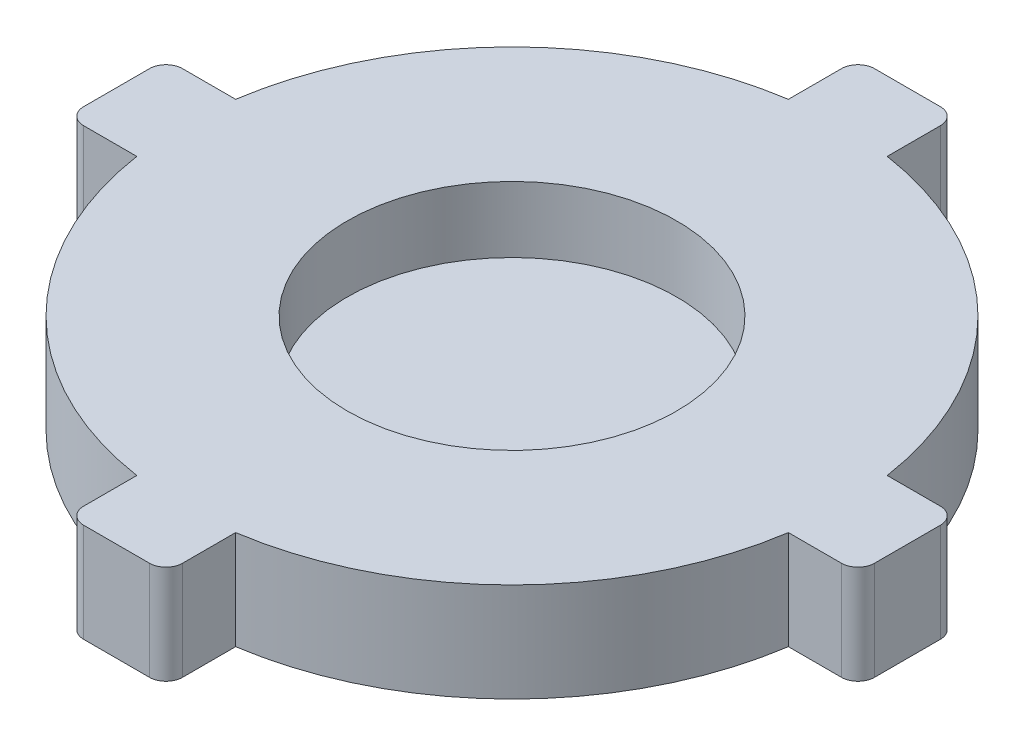
SolidWorks part; units mm, degrees
note: The reader was unsure of these and kept them because the rebuilt part matched: shared geometry of "Sketch1<7>".
material "ENPH 253 Hardboard"
ref_plane "Front Plane" through (0, 0, 0) normal (0, 0, 1) x (1, 0, 0)
ref_plane "Top Plane" through (0, 0, 0) normal (0, 1, 0) x (1, 0, 0)
ref_plane "Right Plane" through (0, 0, 0) normal (1, 0, 0) x (0, 0, -1)
sketch "Sketch1" plane through (0, 0, 0) normal (0, 1, 0) x (1, 0, 0)
  line L0 (0, 50) -> (0, -50)
  line L1 (-100, 0) -> (100, 0) construction
  line L2 (0, 100) -> (0, -100) construction
  line L3 (-15, 47.697) -> (-15, 115)
  line L4 (-10, 120) -> (10, 120)
  line L5 (15, 115) -> (15, 47.697)
  line L6 (47.697, 15) -> (115, 15)
  line L7 (120, 10) -> (120, -10)
  line L8 (115, -15) -> (47.697, -15)
  line L9 (15, -47.697) -> (15, -115)
  line L10 (10, -120) -> (-10, -120)
  line L11 (-15, -115) -> (-15, -47.697)
  line L12 (-47.697, -15) -> (-115, -15)
  line L13 (-120, -10) -> (-120, 10)
  line L14 (-115, 15) -> (-47.697, 15)
  circle A0 centre (0, 0) radius 50
  circle A1 centre (0, 0) radius 100
  arc A2 (15, 52.915) -> (-15, 52.915) centre (0, 0) ccw
  arc A3 (-15, 115) -> (-10, 120) centre (-10, 115) cw
  arc A4 (10, 120) -> (15, 115) centre (10, 115) cw
  circle A5 centre (0, 0) radius 100
  arc A6 (52.915, -15) -> (52.915, 15) centre (0, 0) ccw
  arc A7 (120, -10) -> (115, -15) centre (115, -10) cw
  arc A8 (115, 15) -> (120, 10) centre (115, 10) cw
  circle A9 centre (0, 0) radius 100
  arc A10 (-15, -52.915) -> (15, -52.915) centre (0, 0) ccw
  arc A11 (-10, -120) -> (-15, -115) centre (-10, -115) cw
  arc A12 (15, -115) -> (10, -120) centre (10, -115) cw
  circle A13 centre (0, 0) radius 100
  arc A14 (-52.915, 15) -> (-52.915, -15) centre (0, 0) ccw
  arc A15 (-120, 10) -> (-115, 15) centre (-115, 10) cw
  arc A16 (-115, -15) -> (-120, -10) centre (-115, -10) cw
  point P56 (0, 0)
  dimension "D1" = 100
  dimension "D2" = 200
  dimension "D6" = 110
  dimension "D7" = 5
  dimension "D8" = 5
  dimension "D3" = 15
  dimension "D4" = 15
  dimension "D5" = 70
  dimension "D9" = 4
extrude "Boss-Extrude3" add sketch "Sketch1" along normal blind 30 contours A1 A0 | A2 L5 A1 L3 | L5 A2 L3 A0 | A4 L4 A3 L3 A1 L5 | A16 L12 A1 L14 A15 L13 | A14 L14 A1 L12 | L3 A1 L14 A0 | L12 A1 L11 A0 | A10 L11 A1 L9 | A12 L9 A1 L11 A11 L10 | L9 A1 L8 A0 | A6 L8 A1 L6 | A8 L6 A1 L8 A7 L7 | L6 A1 L5 A0 | L11 A10 L9 A0 | L8 A6 L6 A0
extrude "Boss-Extrude4" add sketch "Sketch1<7>" along normal blind 10 contours L0 A0 | L0 A0
sketch "Sketch1<7>" plane through (0, 0, 0) normal (0, 1, 0) x (1, 0, 0) same geometry as "Sketch1"
sketch "Sketch2" plane through (0, 30, 0) normal (0, 1, 0) x (1, 0, 0)
  line L0 (0, 0) -> (0, -100) construction
  line L1 (-12.941, -48.2963) -> (-25.8819, -96.5926)
  line L2 (12.941, -48.2963) -> (25.8819, -96.5926)
  line L3 (0, 0) -> (-12.941, -48.2963) construction
  line L4 (0, 0) -> (12.941, -48.2963) construction
  circle A0 centre (0, 0) radius 55
  circle A1 centre (0, 0) radius 100 construction
  circle A2 centre (0, 0) radius 50 construction
  circle A3 centre (0, 0) radius 95
  dimension "D3" = 110
  dimension "D4" = 190
  dimension "D1" = 15
  dimension "D2" = 15
equation "\"D2@Sketch2\"=\"D1@Sketch2\""
equation "\"D4@Sketch1\"=\"D3@Sketch1\""
